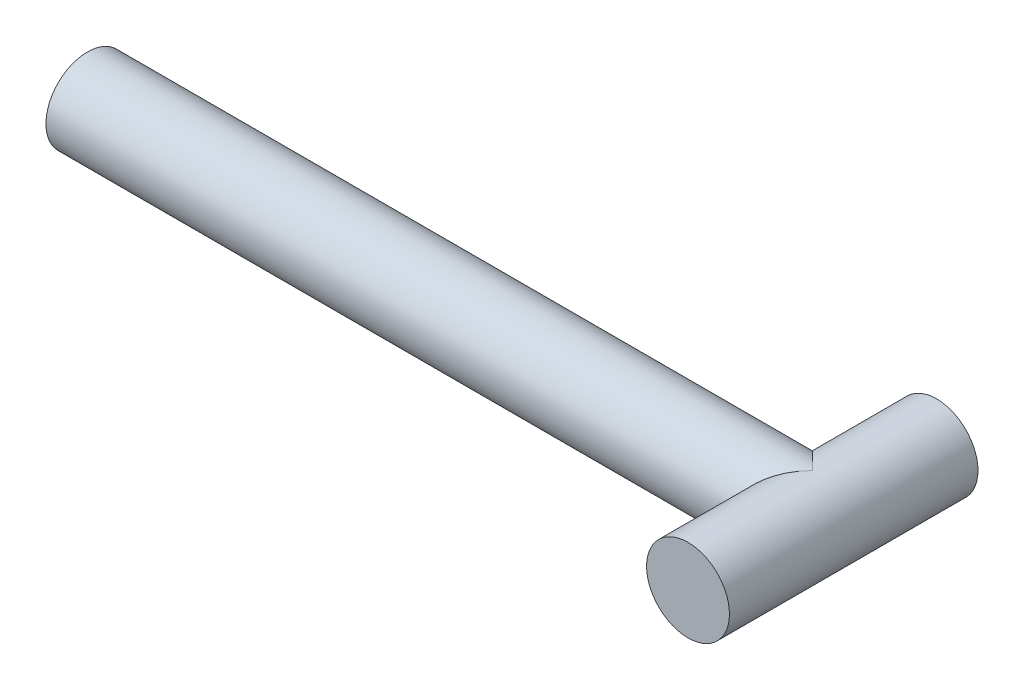
SolidWorks part; units mm, degrees
ref_plane "Front Plane" through (0, 0, 0) normal (0, 0, 1) x (1, 0, 0)
ref_plane "Top Plane" through (0, 0, 0) normal (0, 1, 0) x (1, 0, 0)
ref_plane "Right Plane" through (0, 0, 0) normal (1, 0, 0) x (0, 0, -1)
sketch "Sketch1" plane through (0, 0, 0) normal (1, 0, 0) x (0, 0, -1)
  circle A0 centre (0, 0) radius 4
  dimension "D1" = 8
extrude "Boss-Extrude1" add sketch "Sketch1" against normal blind 70
sketch "Sketch2" plane through (0, 0, 0) normal (0, 0, 1) x (1, 0, 0)
  circle A0 centre (0, 0) radius 4
extrude "Boss-Extrude2" add sketch "Sketch2" against normal blind 12 and the other way blind 12
